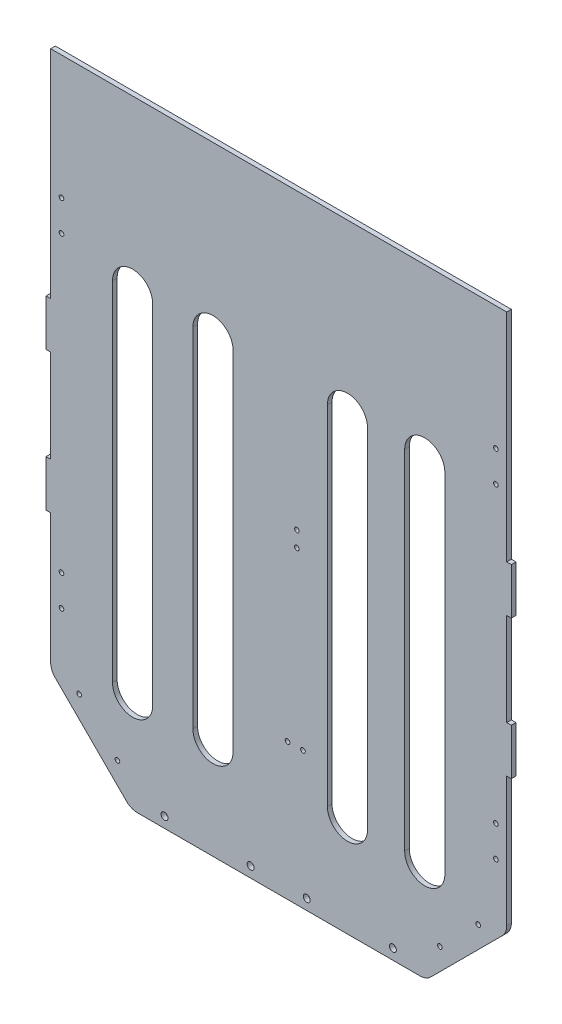
SolidWorks part; units mm, degrees
ref_plane "前视基准面" through (0, 0, 0) normal (0, 0, 1) x (1, 0, 0)
ref_plane "上视基准面" through (0, 0, 0) normal (0, 1, 0) x (1, 0, 0)
ref_plane "右视基准面" through (0, 0, 0) normal (1, 0, 0) x (0, 0, -1)
sketch "草图1" plane through (0, 0, 0) normal (0, 0, 1) x (1, 0, 0)
  line L0 (-147.5, 90) -> (-150.5, 90)
  line L1 (-147.5, 170) -> (147.5, 170)
  line L2 (-147.5, 170) -> (-147.5, 90)
  line L3 (-147.5, -170) -> (147.5, -170)
  line L4 (147.5, 170) -> (147.5, 90)
  line L5 (-147.5, 170) -> (147.5, -170) construction
  line L6 (-147.5, -170) -> (147.5, 170) construction
  line L7 (-150.5, 90) -> (-150.5, 60)
  line L8 (-150.5, 60) -> (-147.5, 60)
  line L9 (-147.5, 60) -> (-147.5, 0)
  line L10 (-147.5, 0) -> (-150.5, 0)
  line L11 (-150.5, 0) -> (-150.5, -30)
  line L12 (-150.5, -30) -> (-147.5, -30)
  line L13 (-147.5, -90) -> (-150.5, -90) construction
  line L14 (-150.5, -90) -> (-150.5, -120) construction
  line L15 (-150.5, -120) -> (-147.5, -120) construction
  line L16 (-147.5, -30) -> (-147.5, -90)
  line L17 (-147.5, -120) -> (-147.5, -170)
  line L18 (0, 0) -> (0, 121.9272) construction
  line L19 (147.5, -90) -> (150.5, -90) construction
  line L20 (150.5, -90) -> (150.5, -120) construction
  line L21 (150.5, -120) -> (147.5, -120) construction
  line L22 (147.5, 0) -> (150.5, 0)
  line L23 (150.5, 0) -> (150.5, -30)
  line L24 (150.5, -30) -> (147.5, -30)
  line L25 (147.5, 90) -> (150.5, 90)
  line L26 (150.5, 90) -> (150.5, 60)
  line L27 (150.5, 60) -> (147.5, 60)
  line L28 (147.5, -120) -> (147.5, -170)
  line L29 (147.5, -30) -> (147.5, -90)
  line L30 (147.5, 60) -> (147.5, 0)
  line L31 (-147.5, -90) -> (-147.5, -120)
  line L32 (147.5, -90) -> (147.5, -120)
  point P0 (0, 0)
  dimension "D1" = 295
  dimension "D2" = 340
  dimension "D3" = 30
  dimension "D4" = 3
  dimension "D5" = 80
  dimension "D6" = 3
  dimension "D7" = 30
  dimension "D8" = 30
  dimension "D9" = 3
  dimension "D10" = 50
  dimension "D11" = 60
extrude "凸台-拉伸1" add sketch "草图1" along normal blind 3
sketch "草图3" plane through (0, 0, 3) normal (0, 0, 1) x (1, 0, 0)
  line L0 (-147.5, -118) -> (-95.5, -170)
  line L1 (-147.5, -30) -> (-147.5, -170) construction
  line L2 (-147.5, -170) -> (147.5, -170) construction
  line L3 (-95.5, -170) -> (-147.5, -170)
  line L4 (-147.5, -170) -> (-147.5, -118)
  line L5 (147.5, -170) -> (147.5, -118)
  line L6 (147.5, -170) -> (147.5, -30) construction
  line L7 (147.5, -118) -> (95.5, -170)
  line L8 (95.5, -170) -> (147.5, -170)
  dimension "D1" = 52
  dimension "D2" = 52
  dimension "D3" = 52
  dimension "D4" = 52
extrude "切除-拉伸2" cut sketch "草图3" against normal through all
fillet "圆角1" [suppressed] radius 5
sketch "草图2" plane through (0, 0, 3) normal (0, 0, 1) x (1, 0, 0)
  line L0 (-95.5, -170) -> (95.5, -170) construction
  line L1 (0, -170) -> (0, -88.9982) construction
  circle A2 centre (73.85, -163.15) radius 2.25 construction
  circle A3 centre (18.15, -163.15) radius 2.25 construction
  circle A4 centre (-73.85, -163.15) radius 2.25 construction
  circle A5 centre (-18.15, -163.15) radius 2.25 construction
  circle A6 centre (11.8005, 40) radius 1.5
  circle A7 centre (11.8005, 30) radius 1.5
  circle A8 centre (73.85, -163.15) radius 2.25 construction
  circle A9 centre (18.15, -163.15) radius 2.25 construction
  circle A10 centre (-73.85, -163.15) radius 2.25 construction
  circle A11 centre (-18.15, -163.15) radius 2.25 construction
  circle A12 centre (-73.85, -163.15) radius 2.25
  circle A13 centre (-18.15, -163.15) radius 2.25
  circle A14 centre (18.15, -163.15) radius 2.25
  circle A15 centre (73.85, -163.15) radius 2.25
  dimension "D1" = 4.5
  dimension "D2" = 4.5
  dimension "D5" = 3
  dimension "D6" = 3
  dimension "D3" = 55.7
  dimension "D4" = 18.15
extrude "切除-拉伸1" cut sketch "草图2" against normal blind 10
sketch "草图4" plane through (0, 0, 3) normal (0, 0, 1) x (1, 0, 0)
  line L0 (147.5, 170) -> (-147.5, 170) construction
  line L1 (147.5, 90) -> (147.5, 170) construction
  line L2 (147.5, -118) -> (147.5, -30) construction
  line L3 (0, 170) -> (0, 113.7599) construction
  circle A0 centre (140.5, 150) radius 1.5
  circle A1 centre (140.5, 130) radius 1.5
  circle A2 centre (140.5, -60) radius 1.5
  circle A3 centre (140.5, -80) radius 1.5
  circle A4 centre (-140.5, -80) radius 1.5
  circle A5 centre (-140.5, -60) radius 1.5
  circle A6 centre (-140.5, 130) radius 1.5
  circle A7 centre (-140.5, 150) radius 1.5
  dimension "D1" = 20
  dimension "D2" = 20
  dimension "D3" = 190
  dimension "D4" = 20
  dimension "D5" = 7
  dimension "D6" = 7
  dimension "D7" = 7
  dimension "D8" = 7
  dimension "D9" = 3
  dimension "D10" = 3
  dimension "D11" = 3
  dimension "D12" = 3
extrude "切除-拉伸3" cut sketch "草图4" against normal through all
sketch "草图5" plane through (0, 0, 3) normal (0, 0, 1) x (1, 0, 0)
  line L0 (-94.5, 120) -> (-94.5, -105) construction
  line L1 (-81.5, 120) -> (-81.5, -105)
  line L2 (-107.5, 120) -> (-107.5, -105)
  line L3 (147.5, 170) -> (-147.5, 170) construction
  line L4 (-147.5, 60) -> (-147.5, 0) construction
  line L5 (-42.5, 120) -> (-42.5, -105) construction
  line L6 (-29.5, 120) -> (-29.5, -105)
  line L7 (-55.5, 120) -> (-55.5, -105)
  line L8 (44.5, 120) -> (44.5, -105) construction
  line L9 (57.5, 120) -> (57.5, -105)
  line L10 (31.5, 120) -> (31.5, -105)
  line L11 (94.5, 120) -> (94.5, -105) construction
  line L12 (107.5, 120) -> (107.5, -105)
  line L13 (81.5, 120) -> (81.5, -105)
  arc A0 (-81.5, 120) -> (-107.5, 120) centre (-94.5, 120) ccw
  arc A1 (-107.5, -105) -> (-81.5, -105) centre (-94.5, -105) ccw
  arc A2 (-29.5, 120) -> (-55.5, 120) centre (-42.5, 120) ccw
  arc A3 (-55.5, -105) -> (-29.5, -105) centre (-42.5, -105) ccw
  arc A4 (57.5, 120) -> (31.5, 120) centre (44.5, 120) ccw
  arc A5 (31.5, -105) -> (57.5, -105) centre (44.5, -105) ccw
  arc A6 (107.5, 120) -> (81.5, 120) centre (94.5, 120) ccw
  arc A7 (81.5, -105) -> (107.5, -105) centre (94.5, -105) ccw
  point P2 (-94.5, 7.5)
  point P14 (-42.5, 7.5)
  point P22 (44.5, 7.5)
  point P29 (94.5, 7.5)
  dimension "D1" = 13
  dimension "D2" = 225
  dimension "D3" = 50
  dimension "D4" = 53
  dimension "D8" = 52
  dimension "D9" = 87
  dimension "D5" = 2
  dimension "D6" = 2
  dimension "D7" = 2
extrude "切除-拉伸4" cut sketch "草图5" against normal through all
fillet "圆角3" radius 10 4 edges at (147.5, -118, 1.5) (95.5, -170, 1.5) (-95.5, -170, 1.5) (-147.5, -118, 1.5)
sketch "草图8" plane through (0, 0, 3) normal (0, 0, 1) x (1, 0, 0)
  line L0 (-129.0441, -122.3138) -> (-104.2954, -147.0625) construction
  line L1 (-98.4289, -167.0711) -> (-144.5711, -120.9289) construction
  line L2 (-147.5, -99.7493) -> (147.5, -99.7493) construction
  line L3 (-147.5, -30) -> (-147.5, -113.8579) construction
  line L4 (147.5, -113.8579) -> (147.5, -30) construction
  line L5 (0, -99.7493) -> (0, -54.3911) construction
  line L6 (129.0441, -122.3138) -> (104.2954, -147.0625) construction
  circle A0 centre (-129.0441, -122.3138) radius 1.5
  circle A1 centre (-104.2954, -147.0625) radius 1.5
  circle A2 centre (104.2954, -147.0625) radius 1.5
  circle A3 centre (129.0441, -122.3138) radius 1.5
  dimension "D1" = 3
  dimension "D2" = 3
  dimension "D3" = 10
  dimension "D4" = 35
extrude "切除-拉伸5" cut sketch "草图8" against normal through all
sketch "草图9" plane through (0, 0, 3) normal (0, 0, 1) x (1, 0, 0)
  line L1 (147.5, 170) -> (-147.5, 170)
  line L2 (147.5, 170) -> (147.5, 230)
  line L3 (147.5, 230) -> (-147.5, 230)
  line L4 (-147.5, 170) -> (-147.5, 230)
  dimension "D1" = 60
extrude "凸台-拉伸2" add sketch "草图9" against normal blind 3
sketch "草图10" plane through (0, 0, 0) normal (0, 0, -1) x (-1, 0, 0)
  circle A0 centre (-15.7145, -81.4977) radius 1.5
  circle A1 centre (-5.7145, -81.4977) radius 1.5
extrude "切除-拉伸6" cut sketch "草图10" against normal blind 10
